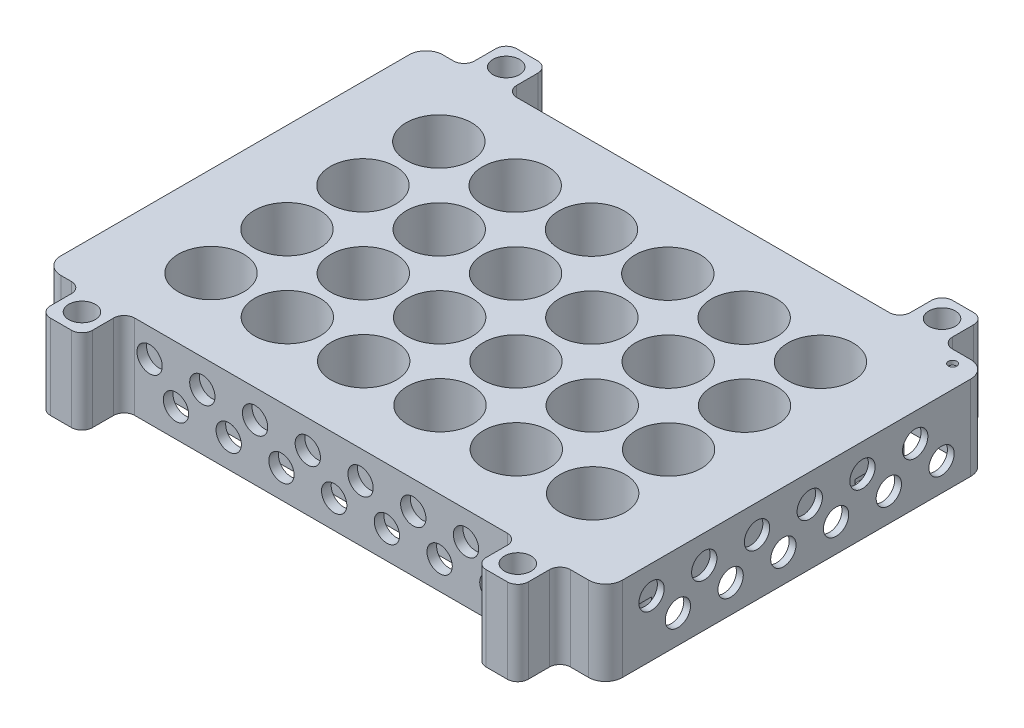
SolidWorks part; units mm, degrees
ref_plane "Front Plane" through (0, 0, 0) normal (0, 0, 1) x (1, 0, 0)
ref_plane "Top Plane" through (0, 0, 0) normal (0, 1, 0) x (1, 0, 0)
ref_plane "Right Plane" through (0, 0, 0) normal (1, 0, 0) x (0, 0, -1)
sketch "Sketch1" plane through (0, 0, 0) normal (0, 1, 0) x (1, 0, 0)
  line L1 (0, 0) -> (157.864, 0)
  line L2 (0, 0) -> (0, -90.551)
  line L3 (0, -90.551) -> (157.864, -90.551)
  line L4 (157.864, 0) -> (157.864, -90.551)
  dimension "D1" = 157.864
  dimension "D2" = 90.551
extrude "Boss-Extrude1" add sketch "Sketch1" along normal blind 24.5
sketch "Sketch39" plane through (0, 24.5, 0) normal (0, 1, 0) x (1, 0, 0)
  line L0 (37.0058, -18.5555) -> (30.949, -18.5555)
  line L1 (30.949, -18.5555) -> (30.4082, -19.0884)
  line L2 (30.4082, -19.0884) -> (30.4082, -25.1854)
  line L3 (30.4082, -25.1854) -> (37.0058, -25.1854)
  line L4 (37.0058, -18.5555) -> (37.0058, -25.1854)
  line L5 (30.4082, -25.1854) -> (37.0058, -18.5555) construction
  line L6 (55.0958, -11.3656) -> (49.039, -11.3656)
  line L7 (49.039, -11.3656) -> (48.4982, -11.8986)
  line L8 (48.4982, -11.8986) -> (48.4982, -17.9955)
  line L9 (48.4982, -17.9955) -> (55.0958, -17.9955)
  line L10 (55.0958, -11.3656) -> (55.0958, -17.9955)
  line L11 (48.4982, -17.9955) -> (55.0958, -11.3656) construction
  line L12 (73.1858, -11.3656) -> (67.129, -11.3656)
  line L13 (67.129, -11.3656) -> (66.5882, -11.8986)
  line L14 (66.5882, -11.8986) -> (66.5882, -17.9955)
  line L15 (66.5882, -17.9955) -> (73.1858, -17.9955)
  line L16 (73.1858, -11.3656) -> (73.1858, -17.9955)
  line L17 (66.5882, -17.9955) -> (73.1858, -11.3656) construction
  line L18 (91.2758, -11.3656) -> (85.219, -11.3656)
  line L19 (85.219, -11.3656) -> (84.6782, -11.8986)
  line L20 (84.6782, -11.8986) -> (84.6782, -17.9955)
  line L21 (84.6782, -17.9955) -> (91.2758, -17.9955)
  line L22 (91.2758, -11.3656) -> (91.2758, -17.9955)
  line L23 (84.6782, -17.9955) -> (91.2758, -11.3656) construction
  line L24 (109.3658, -11.3656) -> (103.309, -11.3656)
  line L25 (103.309, -11.3656) -> (102.7682, -11.8986)
  line L26 (102.7682, -11.8986) -> (102.7682, -17.9955)
  line L27 (102.7682, -17.9955) -> (109.3658, -17.9955)
  line L28 (109.3658, -11.3656) -> (109.3658, -17.9955)
  line L29 (102.7682, -17.9955) -> (109.3658, -11.3656) construction
  line L30 (127.4558, -11.3656) -> (121.399, -11.3656)
  line L31 (121.399, -11.3656) -> (120.8582, -11.8986)
  line L32 (120.8582, -11.8986) -> (120.8582, -17.9955)
  line L33 (120.8582, -17.9955) -> (127.4558, -17.9955)
  line L34 (127.4558, -11.3656) -> (127.4558, -17.9955)
  line L35 (120.8582, -17.9955) -> (127.4558, -11.3656) construction
  line L36 (55.0958, -29.3656) -> (49.039, -29.3656)
  line L37 (49.039, -29.3656) -> (48.4982, -29.8986)
  line L38 (48.4982, -29.8986) -> (48.4982, -35.9955)
  line L39 (48.4982, -35.9955) -> (55.0958, -35.9955)
  line L40 (55.0958, -29.3656) -> (55.0958, -35.9955)
  line L41 (48.4982, -35.9955) -> (55.0958, -29.3656) construction
  line L42 (73.1858, -29.3656) -> (67.129, -29.3656)
  line L43 (67.129, -29.3656) -> (66.5882, -29.8986)
  line L44 (66.5882, -29.8986) -> (66.5882, -35.9955)
  line L45 (66.5882, -35.9955) -> (73.1858, -35.9955)
  line L46 (73.1858, -29.3656) -> (73.1858, -35.9955)
  line L47 (66.5882, -35.9955) -> (73.1858, -29.3656) construction
  line L48 (91.2758, -29.3656) -> (85.219, -29.3656)
  line L49 (85.219, -29.3656) -> (84.6782, -29.8986)
  line L50 (84.6782, -29.8986) -> (84.6782, -35.9955)
  line L51 (84.6782, -35.9955) -> (91.2758, -35.9955)
  line L52 (91.2758, -29.3656) -> (91.2758, -35.9955)
  line L53 (84.6782, -35.9955) -> (91.2758, -29.3656) construction
  line L54 (109.3658, -29.3656) -> (103.309, -29.3656)
  line L55 (103.309, -29.3656) -> (102.7682, -29.8986)
  line L56 (102.7682, -29.8986) -> (102.7682, -35.9955)
  line L57 (102.7682, -35.9955) -> (109.3658, -35.9955)
  line L58 (109.3658, -29.3656) -> (109.3658, -35.9955)
  line L59 (102.7682, -35.9955) -> (109.3658, -29.3656) construction
  line L60 (127.4558, -29.3656) -> (121.399, -29.3656)
  line L61 (121.399, -29.3656) -> (120.8582, -29.8986)
  line L62 (120.8582, -29.8986) -> (120.8582, -35.9955)
  line L63 (120.8582, -35.9955) -> (127.4558, -35.9955)
  line L64 (127.4558, -29.3656) -> (127.4558, -35.9955)
  line L65 (120.8582, -35.9955) -> (127.4558, -29.3656) construction
  line L66 (55.0958, -47.3656) -> (49.039, -47.3656)
  line L67 (49.039, -47.3656) -> (48.4982, -47.8986)
  line L68 (48.4982, -47.8986) -> (48.4982, -53.9955)
  line L69 (48.4982, -53.9955) -> (55.0958, -53.9955)
  line L70 (55.0958, -47.3656) -> (55.0958, -53.9955)
  line L71 (48.4982, -53.9955) -> (55.0958, -47.3656) construction
  line L72 (73.1858, -47.3656) -> (67.129, -47.3656)
  line L73 (67.129, -47.3656) -> (66.5882, -47.8986)
  line L74 (66.5882, -47.8986) -> (66.5882, -53.9955)
  line L75 (66.5882, -53.9955) -> (73.1858, -53.9955)
  line L76 (73.1858, -47.3656) -> (73.1858, -53.9955)
  line L77 (66.5882, -53.9955) -> (73.1858, -47.3656) construction
  line L78 (91.2758, -47.3656) -> (85.219, -47.3656)
  line L79 (85.219, -47.3656) -> (84.6782, -47.8986)
  line L80 (84.6782, -47.8986) -> (84.6782, -53.9955)
  line L81 (84.6782, -53.9955) -> (91.2758, -53.9955)
  line L82 (91.2758, -47.3656) -> (91.2758, -53.9955)
  line L83 (84.6782, -53.9955) -> (91.2758, -47.3656) construction
  line L84 (109.3658, -47.3656) -> (103.309, -47.3656)
  line L85 (103.309, -47.3656) -> (102.7682, -47.8986)
  line L86 (102.7682, -47.8986) -> (102.7682, -53.9955)
  line L87 (102.7682, -53.9955) -> (109.3658, -53.9955)
  line L88 (109.3658, -47.3656) -> (109.3658, -53.9955)
  line L89 (102.7682, -53.9955) -> (109.3658, -47.3656) construction
  line L90 (127.4558, -47.3656) -> (121.399, -47.3656)
  line L91 (121.399, -47.3656) -> (120.8582, -47.8986)
  line L92 (120.8582, -47.8986) -> (120.8582, -53.9955)
  line L93 (120.8582, -53.9955) -> (127.4558, -53.9955)
  line L94 (127.4558, -47.3656) -> (127.4558, -53.9955)
  line L95 (120.8582, -53.9955) -> (127.4558, -47.3656) construction
  line L96 (55.0958, -65.3656) -> (49.039, -65.3656)
  line L97 (49.039, -65.3656) -> (48.4982, -65.8986)
  line L98 (48.4982, -65.8986) -> (48.4982, -71.9955)
  line L99 (48.4982, -71.9955) -> (55.0958, -71.9955)
  line L100 (55.0958, -65.3656) -> (55.0958, -71.9955)
  line L101 (48.4982, -71.9955) -> (55.0958, -65.3656) construction
  line L102 (73.1858, -65.3656) -> (67.129, -65.3656)
  line L103 (67.129, -65.3656) -> (66.5882, -65.8986)
  line L104 (66.5882, -65.8986) -> (66.5882, -71.9955)
  line L105 (66.5882, -71.9955) -> (73.1858, -71.9955)
  line L106 (73.1858, -65.3656) -> (73.1858, -71.9955)
  line L107 (66.5882, -71.9955) -> (73.1858, -65.3656) construction
  line L108 (91.2758, -65.3656) -> (85.219, -65.3656)
  line L109 (85.219, -65.3656) -> (84.6782, -65.8986)
  line L110 (84.6782, -65.8986) -> (84.6782, -71.9955)
  line L111 (84.6782, -71.9955) -> (91.2758, -71.9955)
  line L112 (91.2758, -65.3656) -> (91.2758, -71.9955)
  line L113 (84.6782, -71.9955) -> (91.2758, -65.3656) construction
  line L114 (109.3658, -65.3656) -> (103.309, -65.3656)
  line L115 (103.309, -65.3656) -> (102.7682, -65.8986)
  line L116 (102.7682, -65.8986) -> (102.7682, -71.9955)
  line L117 (102.7682, -71.9955) -> (109.3658, -71.9955)
  line L118 (109.3658, -65.3656) -> (109.3658, -71.9955)
  line L119 (102.7682, -71.9955) -> (109.3658, -65.3656) construction
  line L120 (127.4558, -65.3656) -> (121.399, -65.3656)
  line L121 (121.399, -65.3656) -> (120.8582, -65.8986)
  line L122 (120.8582, -65.8986) -> (120.8582, -71.9955)
  line L123 (120.8582, -71.9955) -> (127.4558, -71.9955)
  line L124 (127.4558, -65.3656) -> (127.4558, -71.9955)
  line L125 (120.8582, -71.9955) -> (127.4558, -65.3656) construction
  line L126 (37.0058, -29.3656) -> (30.949, -29.3656)
  line L127 (30.949, -29.3656) -> (30.4082, -29.8986)
  line L128 (30.4082, -29.8986) -> (30.4082, -35.9955)
  line L129 (30.4082, -35.9955) -> (37.0058, -35.9955)
  line L130 (37.0058, -29.3656) -> (37.0058, -35.9955)
  line L131 (30.4082, -35.9955) -> (37.0058, -29.3656) construction
  line L132 (37.0058, -47.3656) -> (30.949, -47.3656)
  line L133 (30.949, -47.3656) -> (30.4082, -47.8986)
  line L134 (30.4082, -47.8986) -> (30.4082, -53.9955)
  line L135 (30.4082, -53.9955) -> (37.0058, -53.9955)
  line L136 (37.0058, -47.3656) -> (37.0058, -53.9955)
  line L137 (30.4082, -53.9955) -> (37.0058, -47.3656) construction
  line L138 (37.0058, -65.3656) -> (30.949, -65.3656)
  line L139 (30.949, -65.3656) -> (30.4082, -65.8986)
  line L140 (30.4082, -65.8986) -> (30.4082, -71.9955)
  line L141 (30.4082, -71.9955) -> (37.0058, -71.9955)
  line L142 (37.0058, -65.3656) -> (37.0058, -71.9955)
  line L143 (30.4082, -71.9955) -> (37.0058, -65.3656) construction
  line L144 (37.0058, -11.3656) -> (30.949, -11.3656)
  line L145 (30.949, -11.3656) -> (30.4082, -11.8986)
  line L146 (30.4082, -11.8986) -> (30.4082, -17.9955)
  line L147 (30.4082, -17.9955) -> (37.0058, -17.9955)
  line L148 (37.0058, -11.3656) -> (37.0058, -17.9955)
  line L149 (30.4082, -17.9955) -> (37.0058, -11.3656) construction
  line L150 (48.4982, -25.1854) -> (55.0958, -25.1854)
  line L151 (55.0958, -18.5555) -> (55.0958, -25.1854)
  line L152 (55.0958, -18.5555) -> (49.039, -18.5555)
  line L153 (49.039, -18.5555) -> (48.4982, -19.0884)
  line L154 (48.4982, -19.0884) -> (48.4982, -25.1854)
  line L155 (48.4982, -25.1854) -> (55.0958, -18.5555) construction
  line L156 (66.5882, -25.1854) -> (73.1858, -25.1854)
  line L157 (73.1858, -18.5555) -> (73.1858, -25.1854)
  line L158 (73.1858, -18.5555) -> (67.129, -18.5555)
  line L159 (67.129, -18.5555) -> (66.5882, -19.0884)
  line L160 (66.5882, -19.0884) -> (66.5882, -25.1854)
  line L161 (66.5882, -25.1854) -> (73.1858, -18.5555) construction
  line L162 (84.6782, -25.1854) -> (91.2758, -25.1854)
  line L163 (91.2758, -18.5555) -> (91.2758, -25.1854)
  line L164 (91.2758, -18.5555) -> (85.219, -18.5555)
  line L165 (85.219, -18.5555) -> (84.6782, -19.0884)
  line L166 (84.6782, -19.0884) -> (84.6782, -25.1854)
  line L167 (84.6782, -25.1854) -> (91.2758, -18.5555) construction
  line L168 (102.7682, -25.1854) -> (109.3658, -25.1854)
  line L169 (109.3658, -18.5555) -> (109.3658, -25.1854)
  line L170 (109.3658, -18.5555) -> (103.309, -18.5555)
  line L171 (103.309, -18.5555) -> (102.7682, -19.0884)
  line L172 (102.7682, -19.0884) -> (102.7682, -25.1854)
  line L173 (102.7682, -25.1854) -> (109.3658, -18.5555) construction
  line L174 (120.8582, -25.1854) -> (127.4558, -25.1854)
  line L175 (127.4558, -18.5555) -> (127.4558, -25.1854)
  line L176 (127.4558, -18.5555) -> (121.399, -18.5555)
  line L177 (121.399, -18.5555) -> (120.8582, -19.0884)
  line L178 (120.8582, -19.0884) -> (120.8582, -25.1854)
  line L179 (120.8582, -25.1854) -> (127.4558, -18.5555) construction
  line L180 (48.4982, -43.1854) -> (55.0958, -43.1854)
  line L181 (55.0958, -36.5555) -> (55.0958, -43.1854)
  line L182 (55.0958, -36.5555) -> (49.039, -36.5555)
  line L183 (49.039, -36.5555) -> (48.4982, -37.0884)
  line L184 (48.4982, -37.0884) -> (48.4982, -43.1854)
  line L185 (48.4982, -43.1854) -> (55.0958, -36.5555) construction
  line L186 (66.5882, -43.1854) -> (73.1858, -43.1854)
  line L187 (73.1858, -36.5555) -> (73.1858, -43.1854)
  line L188 (73.1858, -36.5555) -> (67.129, -36.5555)
  line L189 (67.129, -36.5555) -> (66.5882, -37.0884)
  line L190 (66.5882, -37.0884) -> (66.5882, -43.1854)
  line L191 (66.5882, -43.1854) -> (73.1858, -36.5555) construction
  line L192 (84.6782, -43.1854) -> (91.2758, -43.1854)
  line L193 (91.2758, -36.5555) -> (91.2758, -43.1854)
  line L194 (91.2758, -36.5555) -> (85.219, -36.5555)
  line L195 (85.219, -36.5555) -> (84.6782, -37.0884)
  line L196 (84.6782, -37.0884) -> (84.6782, -43.1854)
  line L197 (84.6782, -43.1854) -> (91.2758, -36.5555) construction
  line L198 (102.7682, -43.1854) -> (109.3658, -43.1854)
  line L199 (109.3658, -36.5555) -> (109.3658, -43.1854)
  line L200 (109.3658, -36.5555) -> (103.309, -36.5555)
  line L201 (103.309, -36.5555) -> (102.7682, -37.0884)
  line L202 (102.7682, -37.0884) -> (102.7682, -43.1854)
  line L203 (102.7682, -43.1854) -> (109.3658, -36.5555) construction
  line L204 (120.8582, -43.1854) -> (127.4558, -43.1854)
  line L205 (127.4558, -36.5555) -> (127.4558, -43.1854)
  line L206 (127.4558, -36.5555) -> (121.399, -36.5555)
  line L207 (121.399, -36.5555) -> (120.8582, -37.0884)
  line L208 (120.8582, -37.0884) -> (120.8582, -43.1854)
  line L209 (120.8582, -43.1854) -> (127.4558, -36.5555) construction
  line L210 (48.4982, -61.1854) -> (55.0958, -61.1854)
  line L211 (55.0958, -54.5555) -> (55.0958, -61.1854)
  line L212 (55.0958, -54.5555) -> (49.039, -54.5555)
  line L213 (49.039, -54.5555) -> (48.4982, -55.0884)
  line L214 (48.4982, -55.0884) -> (48.4982, -61.1854)
  line L215 (48.4982, -61.1854) -> (55.0958, -54.5555) construction
  line L216 (66.5882, -61.1854) -> (73.1858, -61.1854)
  line L217 (73.1858, -54.5555) -> (73.1858, -61.1854)
  line L218 (73.1858, -54.5555) -> (67.129, -54.5555)
  line L219 (67.129, -54.5555) -> (66.5882, -55.0884)
  line L220 (66.5882, -55.0884) -> (66.5882, -61.1854)
  line L221 (66.5882, -61.1854) -> (73.1858, -54.5555) construction
  line L222 (84.6782, -61.1854) -> (91.2758, -61.1854)
  line L223 (91.2758, -54.5555) -> (91.2758, -61.1854)
  line L224 (91.2758, -54.5555) -> (85.219, -54.5555)
  line L225 (85.219, -54.5555) -> (84.6782, -55.0884)
  line L226 (84.6782, -55.0884) -> (84.6782, -61.1854)
  line L227 (84.6782, -61.1854) -> (91.2758, -54.5555) construction
  line L228 (102.7682, -61.1854) -> (109.3658, -61.1854)
  line L229 (109.3658, -54.5555) -> (109.3658, -61.1854)
  line L230 (109.3658, -54.5555) -> (103.309, -54.5555)
  line L231 (103.309, -54.5555) -> (102.7682, -55.0884)
  line L232 (102.7682, -55.0884) -> (102.7682, -61.1854)
  line L233 (102.7682, -61.1854) -> (109.3658, -54.5555) construction
  line L234 (120.8582, -61.1854) -> (127.4558, -61.1854)
  line L235 (127.4558, -54.5555) -> (127.4558, -61.1854)
  line L236 (127.4558, -54.5555) -> (121.399, -54.5555)
  line L237 (121.399, -54.5555) -> (120.8582, -55.0884)
  line L238 (120.8582, -55.0884) -> (120.8582, -61.1854)
  line L239 (120.8582, -61.1854) -> (127.4558, -54.5555) construction
  line L240 (48.4982, -79.1854) -> (55.0958, -79.1854)
  line L241 (55.0958, -72.5555) -> (55.0958, -79.1854)
  line L242 (55.0958, -72.5555) -> (49.039, -72.5555)
  line L243 (49.039, -72.5555) -> (48.4982, -73.0884)
  line L244 (48.4982, -73.0884) -> (48.4982, -79.1854)
  line L245 (48.4982, -79.1854) -> (55.0958, -72.5555) construction
  line L246 (66.5882, -79.1854) -> (73.1858, -79.1854)
  line L247 (73.1858, -72.5555) -> (73.1858, -79.1854)
  line L248 (73.1858, -72.5555) -> (67.129, -72.5555)
  line L249 (67.129, -72.5555) -> (66.5882, -73.0884)
  line L250 (66.5882, -73.0884) -> (66.5882, -79.1854)
  line L251 (66.5882, -79.1854) -> (73.1858, -72.5555) construction
  line L252 (84.6782, -79.1854) -> (91.2758, -79.1854)
  line L253 (91.2758, -72.5555) -> (91.2758, -79.1854)
  line L254 (91.2758, -72.5555) -> (85.219, -72.5555)
  line L255 (85.219, -72.5555) -> (84.6782, -73.0884)
  line L256 (84.6782, -73.0884) -> (84.6782, -79.1854)
  line L257 (84.6782, -79.1854) -> (91.2758, -72.5555) construction
  line L258 (102.7682, -79.1854) -> (109.3658, -79.1854)
  line L259 (109.3658, -72.5555) -> (109.3658, -79.1854)
  line L260 (109.3658, -72.5555) -> (103.309, -72.5555)
  line L261 (103.309, -72.5555) -> (102.7682, -73.0884)
  line L262 (102.7682, -73.0884) -> (102.7682, -79.1854)
  line L263 (102.7682, -79.1854) -> (109.3658, -72.5555) construction
  line L264 (120.8582, -79.1854) -> (127.4558, -79.1854)
  line L265 (127.4558, -72.5555) -> (127.4558, -79.1854)
  line L266 (127.4558, -72.5555) -> (121.399, -72.5555)
  line L267 (121.399, -72.5555) -> (120.8582, -73.0884)
  line L268 (120.8582, -73.0884) -> (120.8582, -79.1854)
  line L269 (120.8582, -79.1854) -> (127.4558, -72.5555) construction
  line L270 (30.4082, -43.1854) -> (37.0058, -43.1854)
  line L271 (37.0058, -36.5555) -> (37.0058, -43.1854)
  line L272 (37.0058, -36.5555) -> (30.949, -36.5555)
  line L273 (30.949, -36.5555) -> (30.4082, -37.0884)
  line L274 (30.4082, -37.0884) -> (30.4082, -43.1854)
  line L275 (30.4082, -43.1854) -> (37.0058, -36.5555) construction
  line L276 (30.4082, -61.1854) -> (37.0058, -61.1854)
  line L277 (37.0058, -54.5555) -> (37.0058, -61.1854)
  line L278 (37.0058, -54.5555) -> (30.949, -54.5555)
  line L279 (30.949, -54.5555) -> (30.4082, -55.0884)
  line L280 (30.4082, -55.0884) -> (30.4082, -61.1854)
  line L281 (30.4082, -61.1854) -> (37.0058, -54.5555) construction
  line L282 (30.4082, -79.1854) -> (37.0058, -79.1854)
  line L283 (37.0058, -72.5555) -> (37.0058, -79.1854)
  line L284 (37.0058, -72.5555) -> (30.949, -72.5555)
  line L285 (30.949, -72.5555) -> (30.4082, -73.0884)
  line L286 (30.4082, -73.0884) -> (30.4082, -79.1854)
  line L287 (30.4082, -79.1854) -> (37.0058, -72.5555) construction
  line L288 (127.4558, -25.1854) -> (157.864, -25.1854) construction
  line L289 (30.4082, -79.1854) -> (0, -79.1854) construction
  line L290 (0, 0) -> (0, -90.551) construction
  line L291 (30.4082, -79.1854) -> (30.4082, -90.551) construction
  line L292 (0, -90.551) -> (157.864, -90.551) construction
  line L293 (127.4558, -11.3656) -> (127.4558, 0) construction
  line L294 (157.864, 0) -> (0, 0) construction
  line L295 (127.4558, -11.3656) -> (157.864, -11.3656) construction
  line L296 (157.864, -90.551) -> (157.864, 0) construction
  point P0 (33.707, -21.8704)
  point P2 (33.707, -14.6806)
  point P12 (51.797, -14.6806)
  point P18 (69.887, -14.6806)
  point P24 (87.977, -14.6806)
  point P30 (106.067, -14.6806)
  point P36 (124.157, -14.6806)
  point P42 (51.797, -32.6806)
  point P48 (69.887, -32.6806)
  point P54 (87.977, -32.6806)
  point P60 (106.067, -32.6806)
  point P66 (124.157, -32.6806)
  point P72 (51.797, -50.6806)
  point P78 (69.887, -50.6806)
  point P84 (87.977, -50.6806)
  point P90 (106.067, -50.6806)
  point P96 (124.157, -50.6806)
  point P102 (51.797, -68.6806)
  point P108 (69.887, -68.6806)
  point P114 (87.977, -68.6806)
  point P120 (106.067, -68.6806)
  point P126 (124.157, -68.6806)
  point P132 (33.707, -32.6806)
  point P138 (33.707, -50.6806)
  point P144 (33.707, -68.6806)
  point P153 (51.797, -21.8704)
  point P159 (69.887, -21.8704)
  point P165 (87.977, -21.8704)
  point P171 (106.067, -21.8704)
  point P177 (124.157, -21.8704)
  point P183 (51.797, -39.8704)
  point P189 (69.887, -39.8704)
  point P195 (87.977, -39.8704)
  point P201 (106.067, -39.8704)
  point P207 (124.157, -39.8704)
  point P213 (51.797, -57.8704)
  point P219 (69.887, -57.8704)
  point P225 (87.977, -57.8704)
  point P231 (106.067, -57.8704)
  point P237 (124.157, -57.8704)
  point P243 (51.797, -75.8704)
  point P249 (69.887, -75.8704)
  point P255 (87.977, -75.8704)
  point P261 (106.067, -75.8704)
  point P267 (124.157, -75.8704)
  point P273 (33.707, -39.8704)
  point P279 (33.707, -57.8704)
  point P285 (33.707, -75.8704)
  dimension "D2" = 6.0568
  dimension "D3" = 6.0969
  dimension "D4" = 6.5976
  dimension "D5" = 6.6299
  dimension "D6" = 0.7593
  dimension "D7" = 6
  dimension "D8" = 4
  dimension "D9" = 0.56
  dimension "D10" = 6.0568
  dimension "D11" = 6.0969
  dimension "D12" = 6.6299
  dimension "D13" = 6.5976
  dimension "D14" = 0.7593
  dimension "D15" = 6
  dimension "D16" = 4
extrude "Cut-Extrude30" cut sketch "Sketch39" against normal up to surface (24.5 mm away) up to face at (78.932, 0, 45.2755)
sketch "Sketch7" plane through (0, 0, 0) normal (0, -1, 0) x (1, 0, 0)
  line L0 (124.157, 18.2755) -> (157.864, 18.2755) construction
  line L1 (157.864, 90.551) -> (157.864, 0) construction
  line L2 (124.157, 18.2755) -> (124.157, 0) construction
  line L3 (157.864, 0) -> (0, 0) construction
  line L4 (33.707, 18.2755) -> (0, 18.2755) construction
  line L5 (0, 0) -> (0, 90.551) construction
  line L6 (33.707, 72.2755) -> (33.707, 90.551) construction
  line L7 (0, 90.551) -> (157.864, 90.551) construction
  line L8 (33.707, 72.2755) -> (33.707, 90.551) construction
  circle A0 centre (33.707, 72.2755) radius 7.75
  circle A2 centre (51.797, 72.2755) radius 7.75
  circle A3 centre (69.887, 72.2755) radius 7.75
  circle A4 centre (87.977, 72.2755) radius 7.75
  circle A5 centre (106.067, 72.2755) radius 7.75
  circle A6 centre (124.157, 72.2755) radius 7.75
  circle A7 centre (51.797, 54.2755) radius 7.75
  circle A8 centre (69.887, 54.2755) radius 7.75
  circle A9 centre (87.977, 54.2755) radius 7.75
  circle A10 centre (106.067, 54.2755) radius 7.75
  circle A11 centre (124.157, 54.2755) radius 7.75
  circle A12 centre (51.797, 36.2755) radius 7.75
  circle A13 centre (69.887, 36.2755) radius 7.75
  circle A14 centre (87.977, 36.2755) radius 7.75
  circle A15 centre (106.067, 36.2755) radius 7.75
  circle A16 centre (124.157, 36.2755) radius 7.75
  circle A17 centre (51.797, 18.2755) radius 7.75
  circle A18 centre (69.887, 18.2755) radius 7.75
  circle A19 centre (87.977, 18.2755) radius 7.75
  circle A20 centre (106.067, 18.2755) radius 7.75
  circle A21 centre (124.157, 18.2755) radius 7.75
  circle A22 centre (33.707, 54.2755) radius 7.75
  circle A23 centre (33.707, 36.2755) radius 7.75
  circle A24 centre (33.707, 18.2755) radius 7.75
  dimension "D1" = 15.5
  dimension "D6" = 18
  dimension "D3" = 18.09
  dimension "D4" = 18
  dimension "D5" = 18.09
  dimension "D7" = 6
  dimension "D8" = 4
extrude "Cut-Extrude5" cut sketch "Sketch7" along normal blind 17 from surface starting at face at (33.1554, 24.5, 75.314)
sketch "Sketch23" plane through (0, 24.5, 0) normal (0, 1, 0) x (1, 0, 0)
  line L0 (0, -90.551) -> (157.864, -90.551) construction
  line L1 (143.5751, -88.6374) -> (14.2889, -88.6374)
  line L2 (143.5751, -88.6374) -> (143.5751, -1.9136)
  line L3 (143.5751, -1.9136) -> (14.2889, -1.9136)
  line L4 (14.2889, -88.6374) -> (14.2889, -1.9136)
  line L5 (134.6751, -82.6374) -> (23.1889, -82.6374)
  line L6 (134.6751, -82.6374) -> (134.6751, -7.9136)
  line L7 (134.6751, -7.9136) -> (23.1889, -7.9136)
  line L8 (23.1889, -82.6374) -> (23.1889, -7.9136)
  line L9 (157.864, -90.551) -> (157.864, 0) construction
  line L10 (157.864, 0) -> (0, 0) construction
  line L11 (0, 0) -> (0, -90.551) construction
  point P8 (157.864, -45.2755)
  point P17 (0, -45.2755)
  dimension "D1" = 129.2861
  dimension "D2" = 8.9
  dimension "D3" = 8.9
  dimension "D4" = 6
  dimension "D5" = 6
  dimension "D6" = 14.2889
  dimension "D8" = 1.9136
  dimension "D9" = 86.7238
  dimension "D10" = 1.9136
  dimension "D11" = 14.2889
extrude "Cut-Extrude21" cut sketch "Sketch23" against normal blind 4.5
fillet "Fillet7" radius 1 4 edges at (134.6751, 22.25, 7.9136) (23.1889, 22.25, 7.9136) (23.1889, 22.25, 82.6374) (134.6751, 22.25, 82.6374)
fillet "Fillet8" radius 2.75 4 edges at (143.5751, 22.25, 1.9136) (14.2889, 22.25, 1.9136) (14.2889, 22.25, 88.6374) (143.5751, 22.25, 88.6374)
sketch "Sketch26" plane through (0, 24.5, 0) normal (0, 1, 0) x (1, 0, 0)
  line L1 (18.0889, -82.6374) -> (134.6751, -82.6374)
  line L2 (18.0889, -82.6374) -> (18.0889, -7.9136)
  line L3 (18.0889, -7.9136) -> (134.6751, -7.9136)
  line L4 (134.6751, -82.6374) -> (134.6751, -7.9136)
  dimension "D1" = 0
  dimension "D2" = 0
  dimension "D3" = 1
  dimension "D4" = 0
extrude "Cut-Extrude22" cut sketch "Sketch26" against normal blind 3
sketch "Sketch29" plane through (0, 24.5, 0) normal (0, 1, 0) x (1, 0, 0)
  line L0 (157.864, 0) -> (0, 0) construction
  line L1 (157.864, -90.551) -> (145.4887, -90.551)
  line L2 (157.864, -90.551) -> (157.864, 0)
  line L3 (157.864, 0) -> (145.4887, 0)
  line L4 (145.4887, -90.551) -> (145.4887, 0)
  line L6 (0, -90.551) -> (12.3753, -90.551)
  line L7 (0, -90.551) -> (0, 0)
  line L8 (0, 0) -> (12.3753, 0)
  line L9 (12.3753, -90.551) -> (12.3753, 0)
  dimension "D2" = 1.9136
  dimension "D3" = 1.9136
extrude "Cut-Extrude25" cut sketch "Sketch29" against normal through all
fillet "Fillet9" radius 4 4 edges at (12.3753, 12.25, 90.551) (145.4887, 12.25, 90.551) (145.4887, 12.25, 0) (12.3753, 12.25, 0)
sketch "Sketch30" plane through (0, 0, 0) normal (0, -1, 0) x (1, 0, 0)
  line L0 (141.4887, 0) -> (16.3753, 0) construction
  line L1 (134.6936, 0) -> (124.6936, 0)
  line L2 (134.6936, 0) -> (134.6936, -10)
  line L3 (134.6936, -10) -> (124.6936, -10)
  line L4 (124.6936, 0) -> (124.6936, -10)
  line L5 (16.3753, 90.551) -> (141.4887, 90.551) construction
  line L6 (21.3936, 0) -> (31.3936, 0)
  line L7 (21.3936, 0) -> (21.3936, -10)
  line L8 (21.3936, -10) -> (31.3936, -10)
  line L9 (31.3936, 0) -> (31.3936, -10)
  line L10 (134.6936, 90.551) -> (124.6936, 90.551)
  line L11 (134.6936, 90.551) -> (134.6936, 100.551)
  line L12 (134.6936, 100.551) -> (124.6936, 100.551)
  line L13 (124.6936, 90.551) -> (124.6936, 100.551)
  line L14 (124.6936, -10) -> (31.3936, -10) construction
  line L15 (21.3936, 90.551) -> (31.3936, 90.551)
  line L16 (21.3936, 90.551) -> (21.3936, 100.551)
  line L17 (21.3936, 100.551) -> (31.3936, 100.551)
  line L18 (31.3936, 90.551) -> (31.3936, 100.551)
  line L19 (124.6936, 100.551) -> (31.3936, 100.551) construction
  line L20 (31.3936, -10) -> (21.3936, 0) construction
  line L22 (33.707, 0) -> (31.3936, 0) construction
  line L23 (21.3936, 90.551) -> (16.3753, 90.551) construction
  line L24 (33.707, 72.2755) -> (33.707, 18.2755) construction
  line L25 (33.707, 18.2755) -> (33.707, 0) construction
  line L26 (21.3936, -10) -> (31.3936, 0) construction
  line L27 (33.707, 72.2755) -> (33.707, 90.551) construction
  line L28 (31.3936, 90.551) -> (21.3936, 100.551) construction
  line L29 (21.3936, 90.551) -> (31.3936, 100.551) construction
  point P21 (26.3936, -5)
  point P25 (26.3936, 95.551)
  dimension "D1" = 10
  dimension "D2" = 93.3
  dimension "D3" = 7.3134
  dimension "D4" = 7.3134
extrude "Boss-Extrude2" add sketch "Sketch30" against normal through all
sketch "Sketch31" plane through (0, 24.5, 0) normal (0, 1, 0) x (1, 0, 0)
  line L0 (21.3936, 10) -> (31.3936, 0) construction
  line L1 (31.3936, 0) -> (21.3936, 0) construction
  line L2 (21.3936, 0) -> (31.3936, 10) construction
  line L3 (124.6936, 10) -> (134.6936, 0) construction
  line L4 (134.6936, 0) -> (124.6936, 0) construction
  line L5 (124.6936, 0) -> (134.6936, 10) construction
  line L6 (124.6936, -90.551) -> (134.6936, -100.551) construction
  line L7 (134.6936, -100.551) -> (124.6936, -100.551) construction
  line L8 (124.6936, -100.551) -> (134.6936, -90.551) construction
  line L9 (21.3936, -90.551) -> (31.3936, -100.551) construction
  line L10 (31.3936, -100.551) -> (21.3936, -100.551) construction
  line L11 (21.3936, -100.551) -> (31.3936, -90.551) construction
  circle A0 centre (26.3936, 5) radius 3.15
  circle A1 centre (129.6936, 5) radius 3.15
  circle A2 centre (26.3936, -95.551) radius 3.15
  circle A3 centre (129.6936, -95.551) radius 3.15
  dimension "D1" = 6.3
extrude "Cut-Extrude26" cut sketch "Sketch31" against normal through all
fillet "Fillet10" radius 2.5 16 edges at (21.3936, 12.25, 100.551) (124.6936, 12.25, 100.551) (31.3936, 12.25, 100.551) (134.6936, 12.25, 100.551) (134.6936, 12.25, -10) (124.6936, 12.25, -10) (31.3936, 12.25, -10) (21.3936, 12.25, -10) (21.3936, 12.25, 90.551) (31.3936, 12.25, 90.551) (124.6936, 12.25, 90.551) (134.6936, 12.25, 90.551) (134.6936, 12.25, 0) (124.6936, 12.25, 0) (31.3936, 12.25, 0) (21.3936, 12.25, 0)
sketch "Sketch35" plane through (0, 21.5, 0) normal (0, 1, 0) x (1, 0, 0)
  line L0 (33.707, -54.2755) -> (51.797, -72.2755) construction
  line L1 (51.797, -72.2755) -> (33.707, -72.2755) construction
  line L2 (33.707, -72.2755) -> (51.797, -54.2755) construction
  line L3 (106.067, -18.2755) -> (124.157, -36.2755) construction
  line L4 (124.157, -36.2755) -> (106.067, -36.2755) construction
  line L5 (106.067, -36.2755) -> (124.157, -18.2755) construction
  circle A2 centre (115.112, -27.2755) radius 1.4
  circle A3 centre (42.752, -63.2755) radius 1.4
  dimension "D1" = 2.8
extrude "Boss-Extrude3" add sketch "Sketch35" along normal blind 0.75
sketch "Sketch37" plane through (0, 24.5, 0) normal (0, 1, 0) x (1, 0, 0)
  line L1 (-21.3738, -118.5753) -> (214.6608, -118.5753)
  line L2 (-21.3738, -118.5753) -> (-21.3738, 29.3482)
  line L3 (-21.3738, 29.3482) -> (214.6608, 29.3482)
  line L4 (214.6608, -118.5753) -> (214.6608, 29.3482)
extrude "Cut-Extrude29" cut sketch "Sketch37" against normal blind 4.5
sketch "Sketch36" plane through (0, 0, 0) normal (0, -1, 0) x (1, 0, 0)
  line L0 (23.3443, 83.2148) -> (23.3443, 88.2648) construction
  line L1 (14.5962, 88.2648) -> (143.8803, 88.2648)
  line L2 (14.5962, 88.2648) -> (14.5962, 2.0921)
  line L3 (14.5962, 2.0921) -> (143.8803, 2.0921)
  line L4 (143.8803, 88.2648) -> (143.8803, 2.0921)
  line L5 (23.3443, 83.2148) -> (135.1322, 83.2148)
  line L6 (23.3443, 83.2148) -> (23.3443, 7.142)
  line L7 (23.3443, 7.142) -> (135.1322, 7.142)
  line L8 (135.1322, 83.2148) -> (135.1322, 7.142)
  line L9 (23.3443, 83.2148) -> (14.5962, 83.2148) construction
  line L10 (135.1322, 7.142) -> (143.8803, 7.142) construction
  line L11 (135.1322, 7.142) -> (135.1322, 2.0921) construction
extrude "Cut-Extrude28" cut sketch "Sketch36" against normal blind 17
fillet "Fillet11" radius 4 4 edges at (135.1322, 8.5, 83.2148) (23.3443, 8.5, 83.2148) (23.3443, 8.5, 7.142) (135.1322, 8.5, 7.142)
fillet "Fillet12" radius 4 4 edges at (143.8803, 8.5, 88.2648) (14.5962, 8.5, 88.2648) (14.5962, 8.5, 2.0921) (143.8803, 8.5, 2.0921)
sketch "Sketch42" plane through (0, 0, 0) normal (0, -1, 0) x (1, 0, 0)
  line L0 (22.1833, 72.1734) -> (22.1833, 18.1834) construction
  line L1 (22.1833, 18.1834) -> (136.2933, 18.1834) construction
  line L2 (136.2933, 18.1834) -> (136.2933, 72.1734) construction
  line L3 (136.2933, 72.1734) -> (22.1833, 72.1734) construction
  line L4 (22.1833, 72.1734) -> (14.5962, 72.1734) construction
  line L5 (14.5962, 84.2648) -> (14.5962, 6.0921) construction
  line L6 (22.1833, 72.1734) -> (22.1833, 88.2648) construction
  line L7 (139.8803, 88.2648) -> (18.5962, 88.2648) construction
  line L8 (136.2933, 72.1734) -> (143.8803, 72.1734) construction
  line L9 (143.8803, 6.0921) -> (143.8803, 84.2648) construction
  line L10 (136.2933, 18.1834) -> (136.2933, 2.0921) construction
  line L11 (18.5962, 2.0921) -> (139.8803, 2.0921) construction
  circle A0 centre (22.1833, 72.1734) radius 3.1
  circle A1 centre (22.1833, 18.1834) radius 3.1
  circle A2 centre (136.2933, 18.1834) radius 3.1
  circle A3 centre (136.2933, 72.1734) radius 3.1
  dimension "D1" = 6.2
  dimension "D2" = 114.11
  dimension "D3" = 53.99
extrude "Cut-Extrude31" cut sketch "Sketch42" against normal blind 2.75
sketch "Sketch43" plane through (0, 20, 0) normal (0, 1, 0) x (1, 0, 0)
  circle A0 centre (140.1936, -3) radius 1
  dimension "D1" = 2
  dimension "D2" = 3
  dimension "D3" = 3
extrude "Cut-Extrude32" cut sketch "Sketch43" against normal blind 1
chamfer "Chamfer1" [suppressed] distance 0.25 angle 45
sketch "Sketch44" plane through (12.3753, 0, 0) normal (-1, 0, 0) x (0, 0, 1)
  line L0 (10.9005, 6.6667) -> (23.4005, 6.6667) construction
  line L1 (23.4005, 6.6667) -> (35.9005, 6.6667) construction
  line L2 (35.9005, 6.6667) -> (48.4005, 6.6667) construction
  line L3 (48.4005, 6.6667) -> (60.9005, 6.6667) construction
  line L4 (60.9005, 6.6667) -> (73.4005, 6.6667) construction
  line L5 (17.1505, 13.3333) -> (29.6505, 13.3333) construction
  line L6 (29.6505, 13.3333) -> (42.1505, 13.3333) construction
  line L7 (42.1505, 13.3333) -> (54.6505, 13.3333) construction
  line L8 (54.6505, 13.3333) -> (67.1505, 13.3333) construction
  line L9 (67.1505, 13.3333) -> (79.6505, 13.3333) construction
  line L10 (10.9005, 6.6667) -> (17.1505, 13.3333) construction
  line L11 (17.1505, 13.3333) -> (23.4005, 6.6667) construction
  line L12 (10.9005, 6.6667) -> (4, 6.6667) construction
  line L13 (4, 20) -> (4, 0) construction
  line L14 (79.6505, 13.3333) -> (86.551, 13.3333) construction
  line L15 (86.551, 0) -> (86.551, 20) construction
  line L16 (17.1505, 13.3333) -> (17.1505, 20) construction
  line L17 (86.551, 20) -> (4, 20) construction
  line L18 (10.9005, 6.6667) -> (10.9005, 0) construction
  line L19 (86.551, 0) -> (4, 0) construction
  line L20 (17.1505, 13.3333) -> (17.1505, 6.6667) construction
  circle A0 centre (10.9005, 6.6667) radius 3
  circle A1 centre (23.4005, 6.6667) radius 3
  circle A2 centre (35.9005, 6.6667) radius 3
  circle A3 centre (48.4005, 6.6667) radius 3
  circle A4 centre (60.9005, 6.6667) radius 3
  circle A5 centre (73.4005, 6.6667) radius 3
  circle A6 centre (17.1505, 13.3333) radius 3
  circle A7 centre (29.6505, 13.3333) radius 3
  circle A8 centre (42.1505, 13.3333) radius 3
  circle A9 centre (54.6505, 13.3333) radius 3
  circle A10 centre (67.1505, 13.3333) radius 3
  circle A11 centre (79.6505, 13.3333) radius 3
  dimension "D1" = 6
  dimension "D2" = 12.5
extrude "Cut-Extrude33" cut sketch "Sketch44" against normal up to surface (2.2209 mm away) up to face at (14.5962, 8.5, 45.1784)
sketch "Sketch45" plane through (0, 0, 90.551) normal (0, 0, 1) x (1, 0, 0)
  line L0 (37.4186, 13.3333) -> (49.9186, 13.3333) construction
  line L1 (49.9186, 13.3333) -> (62.4186, 13.3333) construction
  line L2 (62.4186, 13.3333) -> (74.9186, 13.3333) construction
  line L3 (74.9186, 13.3333) -> (87.4186, 13.3333) construction
  line L4 (87.4186, 13.3333) -> (99.9186, 13.3333) construction
  line L5 (99.9186, 13.3333) -> (112.4186, 13.3333) construction
  line L6 (118.6686, 6.6667) -> (106.1686, 6.6667) construction
  line L7 (106.1686, 6.6667) -> (93.6686, 6.6667) construction
  line L8 (93.6686, 6.6667) -> (81.1686, 6.6667) construction
  line L9 (81.1686, 6.6667) -> (68.6686, 6.6667) construction
  line L10 (68.6686, 6.6667) -> (56.1686, 6.6667) construction
  line L11 (56.1686, 6.6667) -> (43.6686, 6.6667) construction
  line L12 (43.6686, 6.6667) -> (37.4186, 13.3333) construction
  line L13 (37.4186, 13.3333) -> (49.9186, 13.3333) construction
  line L14 (49.9186, 13.3333) -> (43.6686, 6.6667) construction
  line L15 (37.4186, 13.3333) -> (37.4186, 20) construction
  line L16 (122.1936, 20) -> (33.8936, 20) construction
  line L17 (43.6686, 6.6667) -> (43.6686, 0) construction
  line L18 (33.8936, 0) -> (122.1936, 0) construction
  line L19 (37.4186, 13.3333) -> (33.8936, 13.3333) construction
  line L20 (33.8936, 20) -> (33.8936, 0) construction
  line L21 (118.6686, 6.6667) -> (122.1936, 6.6667) construction
  line L22 (122.1936, 0) -> (122.1936, 20) construction
  line L23 (43.6686, 6.6667) -> (43.6686, 13.3333) construction
  circle A0 centre (37.4186, 13.3333) radius 3
  circle A1 centre (49.9186, 13.3333) radius 3
  circle A2 centre (62.4186, 13.3333) radius 3
  circle A3 centre (74.9186, 13.3333) radius 3
  circle A4 centre (87.4186, 13.3333) radius 3
  circle A5 centre (99.9186, 13.3333) radius 3
  circle A6 centre (112.4186, 13.3333) radius 3
  circle A7 centre (43.6686, 6.6667) radius 3
  circle A8 centre (56.1686, 6.6667) radius 3
  circle A9 centre (68.6686, 6.6667) radius 3
  circle A10 centre (81.1686, 6.6667) radius 3
  circle A11 centre (93.6686, 6.6667) radius 3
  circle A12 centre (106.1686, 6.6667) radius 3
  circle A13 centre (118.6686, 6.6667) radius 3
  dimension "D1" = 6
  dimension "D2" = 12.5
extrude "Cut-Extrude34" cut sketch "Sketch45" against normal up to surface (2.2862 mm away) up to face at (79.2383, 8.5, 88.2648)
sketch "Sketch46" plane through (145.4887, 0, 0) normal (1, 0, 0) x (0, 0, -1)
  line L0 (-79.6505, 13.3333) -> (-67.1505, 13.3333) construction
  line L1 (-67.1505, 13.3333) -> (-54.6505, 13.3333) construction
  line L2 (-54.6505, 13.3333) -> (-42.1505, 13.3333) construction
  line L3 (-42.1505, 13.3333) -> (-29.6505, 13.3333) construction
  line L4 (-29.6505, 13.3333) -> (-17.1505, 13.3333) construction
  line L5 (-73.4005, 6.6667) -> (-60.9005, 6.6667) construction
  line L6 (-60.9005, 6.6667) -> (-48.4005, 6.6667) construction
  line L7 (-48.4005, 6.6667) -> (-35.9005, 6.6667) construction
  line L8 (-35.9005, 6.6667) -> (-23.4005, 6.6667) construction
  line L9 (-23.4005, 6.6667) -> (-10.9005, 6.6667) construction
  line L10 (-67.1505, 13.3333) -> (-79.6505, 13.3333) construction
  line L11 (-79.6505, 13.3333) -> (-73.4005, 6.6667) construction
  line L12 (-73.4005, 6.6667) -> (-67.1505, 13.3333) construction
  line L13 (-79.6505, 13.3333) -> (-79.6505, 20) construction
  line L14 (-4, 20) -> (-86.551, 20) construction
  line L15 (-73.4005, 6.6667) -> (-73.4005, 0) construction
  line L16 (-4, 0) -> (-86.551, 0) construction
  line L17 (-79.6505, 13.3333) -> (-86.551, 13.3333) construction
  line L18 (-86.551, 20) -> (-86.551, 0) construction
  line L19 (-10.9005, 6.6667) -> (-4, 6.6667) construction
  line L20 (-4, 0) -> (-4, 20) construction
  line L21 (-73.4005, 6.6667) -> (-73.4005, 13.3333) construction
  circle A0 centre (-79.6505, 13.3333) radius 3
  circle A1 centre (-67.1505, 13.3333) radius 3
  circle A2 centre (-54.6505, 13.3333) radius 3
  circle A3 centre (-42.1505, 13.3333) radius 3
  circle A4 centre (-29.6505, 13.3333) radius 3
  circle A5 centre (-73.4005, 6.6667) radius 3
  circle A6 centre (-17.1505, 13.3333) radius 3
  circle A7 centre (-60.9005, 6.6667) radius 3
  circle A8 centre (-48.4005, 6.6667) radius 3
  circle A9 centre (-35.9005, 6.6667) radius 3
  circle A10 centre (-23.4005, 6.6667) radius 3
  circle A11 centre (-10.9005, 6.6667) radius 3
  dimension "D1" = 6
  dimension "D2" = 12.5
extrude "Cut-Extrude35" cut sketch "Sketch46" against normal up to surface (1.6084 mm away) up to face at (143.8803, 8.5, 45.1784)
sketch "Sketch47" plane through (0, 0, 0) normal (0, 0, -1) x (-1, 0, 0)
  line L0 (-118.6686, 13.3333) -> (-106.1686, 13.3333) construction
  line L1 (-106.1686, 13.3333) -> (-93.6686, 13.3333) construction
  line L2 (-93.6686, 13.3333) -> (-81.1686, 13.3333) construction
  line L3 (-81.1686, 13.3333) -> (-68.6686, 13.3333) construction
  line L4 (-68.6686, 13.3333) -> (-56.1686, 13.3333) construction
  line L5 (-56.1686, 13.3333) -> (-43.6686, 13.3333) construction
  line L7 (-112.4186, 6.6667) -> (-99.9186, 6.6667) construction
  line L8 (-99.9186, 6.6667) -> (-87.4186, 6.6667) construction
  line L9 (-87.4186, 6.6667) -> (-74.9186, 6.6667) construction
  line L10 (-74.9186, 6.6667) -> (-62.4186, 6.6667) construction
  line L11 (-62.4186, 6.6667) -> (-49.9186, 6.6667) construction
  line L12 (-49.9186, 6.6667) -> (-37.4186, 6.6667) construction
  line L13 (-118.6686, 13.3333) -> (-106.1686, 13.3333) construction
  line L14 (-106.1686, 13.3333) -> (-112.4186, 6.6667) construction
  line L15 (-112.4186, 6.6667) -> (-118.6686, 13.3333) construction
  line L16 (-112.4186, 6.6667) -> (-112.4186, 13.3333) construction
  line L17 (-118.6686, 13.3333) -> (-118.6686, 20) construction
  line L18 (-33.8936, 20) -> (-122.1936, 20) construction
  line L19 (-112.4186, 6.6667) -> (-112.4186, 0) construction
  line L20 (-122.1936, 0) -> (-33.8936, 0) construction
  line L21 (-118.6686, 13.3333) -> (-122.1936, 13.3333) construction
  line L22 (-122.1936, 20) -> (-122.1936, 0) construction
  line L23 (-37.4186, 6.6667) -> (-33.8936, 6.6667) construction
  line L24 (-33.8936, 0) -> (-33.8936, 20) construction
  circle A0 centre (-118.6686, 13.3333) radius 3
  circle A1 centre (-43.6686, 13.3333) radius 3
  circle A2 centre (-81.1686, 13.3333) radius 3
  circle A3 centre (-68.6686, 13.3333) radius 3
  circle A4 centre (-56.1686, 13.3333) radius 3
  circle A6 centre (-93.6686, 13.3333) radius 3
  circle A7 centre (-106.1686, 13.3333) radius 3
  circle A8 centre (-112.4186, 6.6667) radius 3
  circle A9 centre (-99.9186, 6.6667) radius 3
  circle A10 centre (-87.4186, 6.6667) radius 3
  circle A11 centre (-74.9186, 6.6667) radius 3
  circle A12 centre (-62.4186, 6.6667) radius 3
  circle A13 centre (-49.9186, 6.6667) radius 3
  circle A14 centre (-37.4186, 6.6667) radius 3
  dimension "D1" = 6
  dimension "D2" = 12.5
extrude "Cut-Extrude36" cut sketch "Sketch47" against normal up to surface (2.0921 mm away) up to face at (79.2383, 8.5, 2.0921)
